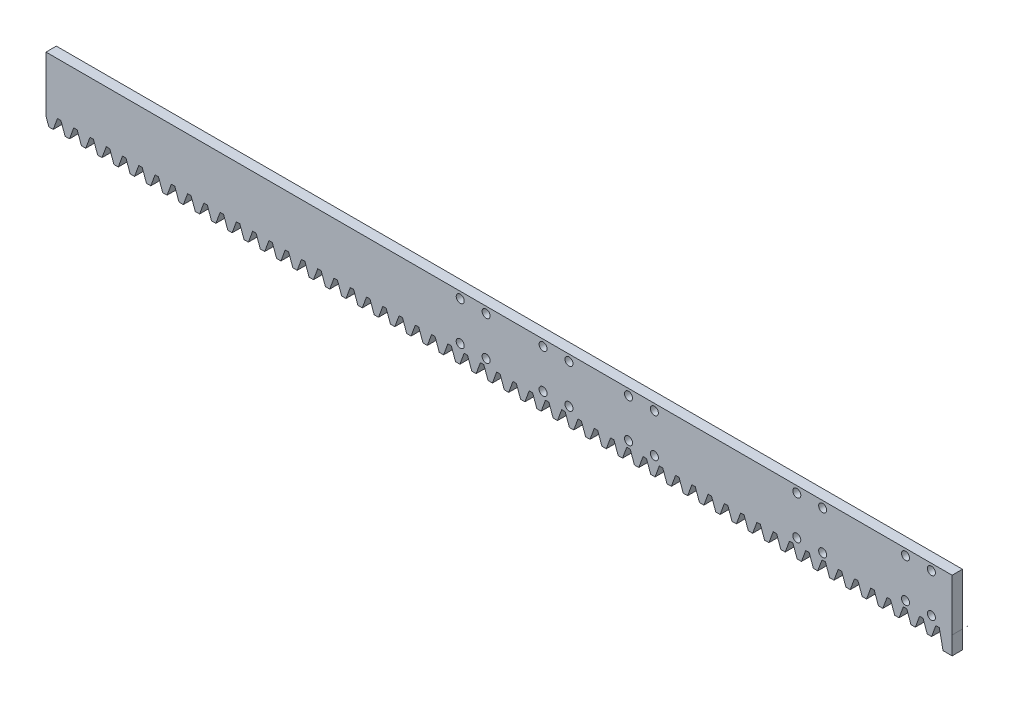
SolidWorks part; units mm, degrees
material "玻纤板"
ref_plane "前视基准面" through (0, 0, 0) normal (0, 0, 1) x (1, 0, 0)
ref_plane "上视基准面" through (0, 0, 0) normal (0, 1, 0) x (1, 0, 0)
ref_plane "右视基准面" through (0, 0, 0) normal (1, 0, 0) x (0, 0, -1)
sketch "草图1" plane through (0, 0, 0) normal (0, 0, 1) x (1, 0, 0)
  line L1 (0, 0) -> (677.26, 0)
  line L2 (0, 0) -> (0, -10)
  line L3 (0, -10) -> (677.26, -10)
  line L4 (677.26, 0) -> (677.26, -10)
  dimension "D1" = 10
  dimension "L" = 677.26
extrude "拉伸1" add sketch "草图1" along normal blind 10
sketch "草图2" plane through (0, 0, 10) normal (0, 0, 1) x (1, 0, 0)
  line L0 (0, 0) -> (1.6379, 4.5)
  line L1 (1.6379, 4.5) -> (3.3236, 4.5)
  line L2 (3.3236, 4.5) -> (4.9614, 0)
  line L3 (677.26, 0) -> (0, 0) construction
  line L4 (0, 0) -> (4.9614, 0)
  line L5 (0.9099, 2.5) -> (4.0515, 2.5) construction
  dimension "D2" = 70
  dimension "alpha" = 110
  dimension "ha" = 2
  dimension "hf" = 2.5
  dimension "S" = 3.1416
extrude "拉伸2" add sketch "草图2" against normal up to surface (10 mm away) up to face at (338.63, -5, 0)
pattern_linear "阵列(线性)1" count 108 spacing 6.2832 along (1, 0, 0) of "拉伸2"
sketch "草图3" plane through (0, 0, 10) normal (0, 0, 1) x (1, 0, 0)
  line L0 (677.26, -10) -> (677.26, 0) construction
  line L1 (0, -10) -> (677.26, -10)
  line L2 (0, -10) -> (0, 8.2552)
  line L3 (0, 8.2552) -> (677.26, 8.2552)
  line L4 (677.26, -10) -> (677.26, 8.2552)
extrude "切除-拉伸1" cut sketch "草图3" against normal through all from offset 4 offset against normal yes
sketch "草图4" plane through (0, 0, 10) normal (0, 0, 1) x (1, 0, 0)
  line L0 (677.26, -10) -> (677.26, 0) construction
  line L1 (0, -10) -> (677.26, -10)
  line L2 (0, -10) -> (0, -15)
  line L3 (0, -15) -> (677.26, -15)
  line L4 (677.26, -10) -> (677.26, -15)
  dimension "D1" = 5
extrude "凸台-拉伸1" add sketch "草图4" against normal up to surface (4 mm away) up to face at (339.4096, 2.1885, 6)
ref_plane "基准面1" through (0, -7.5, 0) normal (0, 1, 0) x (1, 0, 0)
mirror "镜向1" about plane through (0, -7.5, 0) normal (0, 1, 0) of "阵列(线性)1"
sketch "草图6" plane through (0, 0, 10) normal (0, 0, 1) x (1, 0, 0)
  line L1 (0, 0) -> (678.5369, 0)
  line L2 (0, 0) -> (0, 5.6282)
  line L3 (0, 5.6282) -> (678.5369, 5.6282)
  line L4 (678.5369, 0) -> (678.5369, 5.6282)
extrude "切除-拉伸3" cut sketch "草图6" against normal through all both and the other way through all
sketch "草图7" plane through (0, 0, 6) normal (0, 0, -1) x (-1, 0, 0)
  line L1 (-677.26, -15) -> (55.0071, -15)
  line L2 (-677.26, -15) -> (-677.26, -48.5029)
  line L3 (-677.26, -48.5029) -> (55.0071, -48.5029)
  line L4 (55.0071, -15) -> (55.0071, -48.5029)
extrude "切除-拉伸4" cut sketch "草图7" along normal blind 10
sketch "草图8" plane through (0, 0, 0) normal (-1, 0, 0) x (0, 0, 1)
  circle A0 centre (0, 0) radius 50
  dimension "D1" = 100
extrude "长度控制" cut sketch "草图8" against normal offset from surface (327.26 mm away) 350 up to face at (677.26, -7.5, 8)
sketch "草图9" plane through (0, 0, 10) normal (0, 0, 1) x (1, 0, 0)
  line L0 (677.26, -15) -> (677.26, 0) construction
  line L1 (327.26, 0) -> (677.26, 0)
  line L2 (327.26, 0) -> (327.26, 5)
  line L3 (327.26, 5) -> (677.26, 5)
  line L4 (677.26, 0) -> (677.26, 5)
  line L7 (670.9791, -15) -> (672.3008, -15) construction
  point P9 (0, 0)
  point P12 (0, 0)
  point P13 (0, 0)
  point P14 (0, 0)
  dimension "D1" = 20
extrude "凸台-拉伸2" add sketch "草图9" against normal up to surface (4 mm away) up to face at (502.7707, -17.0946, 6)
sketch "草图10" plane through (0, 0, 10) normal (0, 0, 1) x (1, 0, 0)
  line L0 (677.26, -5) -> (653.8371, -5) construction
  line L1 (677.26, -15) -> (677.26, 5) construction
  line L2 (669.26, 2.5) -> (669.26, -12.5) construction
  line L3 (669.26, 2.5) -> (659.26, 2.5) construction
  line L4 (659.26, 2.5) -> (659.26, -12.5) construction
  line L5 (659.26, -12.5) -> (669.26, -12.5) construction
  line L6 (519.26, 2.5) -> (529.26, 2.5) construction
  line L7 (529.26, 2.5) -> (529.26, -12.5) construction
  line L8 (529.26, -12.5) -> (519.26, -12.5) construction
  line L9 (519.26, -12.5) -> (519.26, 2.5) construction
  circle A0 centre (669.26, 2.5) radius 1.55
  circle A1 centre (669.26, -12.5) radius 1.55
  circle A2 centre (659.26, -12.5) radius 1.55
  circle A3 centre (659.26, 2.5) radius 1.55
  circle A4 centre (529.26, -12.5) radius 1.55
  circle A5 centre (529.26, 2.5) radius 1.55
  circle A6 centre (519.26, -12.5) radius 1.55
  circle A7 centre (519.26, 2.5) radius 1.55
  point P1 (677.26, -5)
  point P8 (669.26, -5)
  point P22 (529.26, -5)
  point P23 (581.6331, -12.5)
  dimension "D1" = 15
  dimension "D3" = 3.1
  dimension "D4" = 8
  dimension "D5" = 10
  dimension "D2" = 10
  dimension "D6" = 15
  dimension "D7" = 130
extrude "切除-拉伸6" cut sketch "草图10" against normal through all both and the other way through all
sketch "草图11" plane through (0, 0, 10) normal (0, 0, 1) x (1, 0, 0)
  line L0 (627.26, 2.5) -> (617.26, 2.5) construction
  line L1 (617.26, 2.5) -> (617.26, -12.5) construction
  line L2 (617.26, -12.5) -> (627.26, -12.5) construction
  line L3 (627.26, -12.5) -> (627.26, 2.5) construction
  line L4 (627.26, -5) -> (677.26, -5) construction
  line L5 (677.26, -15) -> (677.26, 5) construction
  circle A0 centre (617.26, 2.5) radius 1.55
  circle A1 centre (627.26, 2.5) radius 1.55
  circle A2 centre (617.26, -12.5) radius 1.55
  circle A3 centre (627.26, -12.5) radius 1.55
  circle A4 centre (659.26, -12.5) radius 1.55 construction
  dimension "D1" = 10
  dimension "D3" = 50
  dimension "D2" = 15
extrude "切除-拉伸7" cut sketch "草图11" against normal through all both and the other way through all
pattern_linear "阵列(线性)2" count 3 spacing 65 along (-1, 0, 0) of "切除-拉伸7"
sketch "草图13" plane through (0, 0, 10) normal (0, 0, 1) x (1, 0, 0)
  line L0 (677.2623, -15) -> (677.2623, -22)
  line L1 (677.2623, -22) -> (673.7623, -22)
  line L2 (673.7623, -22) -> (672.3008, -15)
  line L3 (677.2623, -15) -> (672.3008, -15)
  dimension "D1" = 3.5
  dimension "D2" = 7
extrude "凸台-拉伸3" add sketch "草图13" against normal up to surface (4 mm away) up to face at (550.71, -12.5, 6)
move or copy body "实体-移动/复制1" [suppressed] bodies to move or copy 111
move or copy body "实体-移动/复制2" [suppressed] bodies to move or copy 107
equation "\"d\"=\"S@草图2\" * 2"
equation "\"z\"= int(  \"L@草图1\" / (  \"S@草图2\" * 2 ) + 0.5 )"
